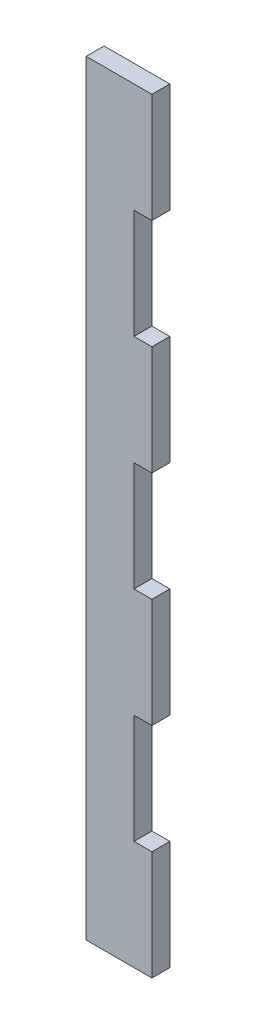
SolidWorks part; units mm, degrees
ref_plane "Front Plane" through (0, 0, 0) normal (0, 0, 1) x (1, 0, 0)
ref_plane "Top Plane" through (0, 0, 0) normal (0, 1, 0) x (1, 0, 0)
ref_plane "Right Plane" through (0, 0, 0) normal (1, 0, 0) x (0, 0, -1)
sketch "Sketch1" plane through (0, 0, 0) normal (0, 0, 1) x (1, 0, 0)
  line L0 (0, 101.6) -> (0, -101.6) construction
  line L1 (-6.35, 101.6) -> (6.35, 101.6)
  line L2 (-6.35, 101.6) -> (-6.35, -101.6)
  line L3 (-6.35, -101.6) -> (6.35, -101.6)
  line L4 (6.35, 101.6) -> (6.35, -101.6)
  line L5 (6.35, 72.5714) -> (6.35, 43.5429)
  line L6 (6.35, 101.6) -> (11.1125, 101.6)
  line L7 (6.35, 101.6) -> (6.35, 72.5714)
  line L8 (6.35, 72.5714) -> (11.1125, 72.5714)
  line L9 (11.1125, 101.6) -> (11.1125, 72.5714)
  line L10 (6.35, 72.5714) -> (11.1125, 72.5714)
  line L11 (11.1125, 72.5714) -> (11.1125, 43.5429)
  line L12 (6.35, 43.5429) -> (11.1125, 43.5429)
  line L13 (6.35, 43.5429) -> (6.35, 14.5143)
  line L14 (6.35, 43.5429) -> (11.1125, 43.5429)
  line L15 (11.1125, 43.5429) -> (11.1125, 14.5143)
  line L16 (6.35, 14.5143) -> (11.1125, 14.5143)
  line L17 (6.35, 14.5143) -> (6.35, -14.5143)
  line L18 (6.35, 14.5143) -> (11.1125, 14.5143)
  line L19 (11.1125, 14.5143) -> (11.1125, -14.5143)
  line L20 (6.35, -14.5143) -> (11.1125, -14.5143)
  line L21 (6.35, -14.5143) -> (6.35, -43.5429)
  line L22 (6.35, -14.5143) -> (11.1125, -14.5143)
  line L23 (11.1125, -14.5143) -> (11.1125, -43.5429)
  line L24 (6.35, -43.5429) -> (11.1125, -43.5429)
  line L25 (6.35, -43.5429) -> (6.35, -72.5714)
  line L26 (6.35, -43.5429) -> (11.1125, -43.5429)
  line L27 (11.1125, -43.5429) -> (11.1125, -72.5714)
  line L28 (6.35, -72.5714) -> (11.1125, -72.5714)
  line L29 (6.35, -72.5714) -> (6.35, -101.6)
  line L30 (6.35, -72.5714) -> (11.1125, -72.5714)
  line L31 (11.1125, -72.5714) -> (11.1125, -101.6)
  line L32 (6.35, -101.6) -> (11.1125, -101.6)
  point P6 (0, 0)
  dimension "D2" = 12.7
  dimension "D1" = 203.2
  dimension "D3" = 29.0286
  dimension "D4" = 4.7625
  dimension "D5" = 7
extrude "Boss-Extrude1" add sketch "Sketch1" along normal blind 4.7625 contours L0 L1 L2 L3 | L1 L0 L3 L4 | L9 L6 L4 L8 | L4 L16 L15 L12 | L4 L24 L23 L20 | L4 L32 L31 L28 region at (3.175, 0, 0) region at (-3.175, 0, 0) region at (8.7312, 87.0857, 0) region at (8.7313, -87.0857, 0) region at (8.7313, 29.0286, 0) region at (8.7313, -29.0286, 0)
equation "\"Height\"= 12in"
equation "\"Depth\"= 7in"
equation "\"WallThickness\"= 0.1875in"
equation "\"FloorThickness\"= 0.1875in"
equation "\"Width\" = 30in"
equation "\"D1@Boss-Extrude1\"=\"WallThickness\""
equation "\"D3@Sketch1\"=\"D1@Sketch1\"/\"D5@Sketch1\""
equation "\"D4@Sketch1\"=\"WallThickness\""
